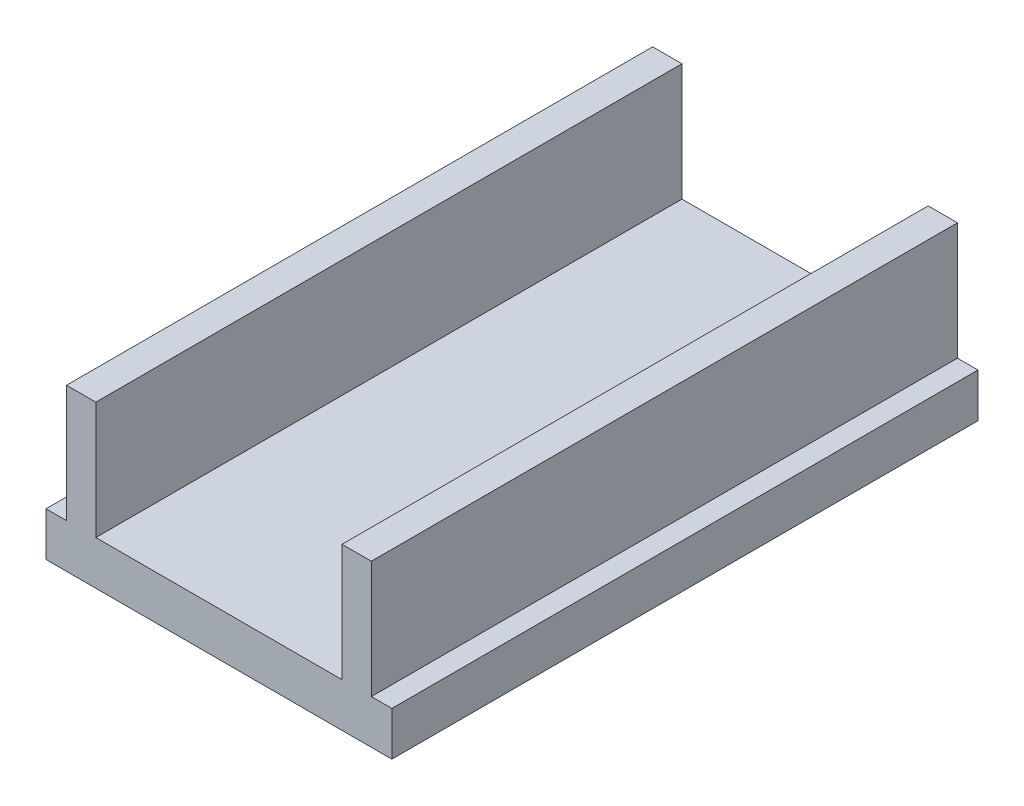
SolidWorks part; units mm, degrees
ref_plane "Front Plane" through (0, 0, 0) normal (0, 0, 1) x (1, 0, 0)
ref_plane "Top Plane" through (0, 0, 0) normal (0, 1, 0) x (1, 0, 0)
ref_plane "Right Plane" through (0, 0, 0) normal (1, 0, 0) x (0, 0, -1)
sketch "Sketch1" plane through (0, 0, 0) normal (0, 1, 0) x (1, 0, 0)
  line L0 (-5.5819, 12.8456) -> (-5.5819, -7.1544)
  line L1 (-6.2819, 12.8456) -> (5.5181, 12.8456)
  line L2 (-6.2819, 12.8456) -> (-6.2819, -7.1544)
  line L3 (-6.2819, -7.1544) -> (5.5181, -7.1544)
  line L4 (5.5181, 12.8456) -> (5.5181, -7.1544)
  line L5 (-5.5819, -7.1544) -> (4.8181, -7.1544)
  line L6 (4.8181, -7.1544) -> (4.8181, 12.8456)
  line L7 (4.8181, 12.8456) -> (-4.5819, 12.8456)
  line L8 (-4.5819, 12.8456) -> (-4.5819, -7.1544)
  line L9 (3.8181, 12.8456) -> (3.8181, -7.1544)
  dimension "D1" = 11.8
  dimension "D2" = 0.7
  dimension "D3" = 1
  dimension "D4" = 1
  dimension "D5" = 0.7
  dimension "D6" = 20
extrude "Boss-Extrude1" add sketch "Sketch1" along normal blind 1.5 contours L2 L3 L0 L1 | L8 L1 L0 L3 | L9 L1 L8 L5 | L7 L9 L3 L6 | L6 L3 L4 L1 region at (-5.0819, 0, -2.8456) region at (-5.9319, 0, -2.8456) region at (-0.3819, 0, -2.8456) region at (4.3181, 0, -2.8456) region at (5.1681, 0, -2.8456)
extrude "Boss-Extrude2" add sketch "Sketch1<3>" along normal blind 4 from surface contours L8 L1 L0 L3 | L7 L9 L3 L6 region at (-5.0819, 0, -2.8456) region at (4.3181, 0, -2.8456) starting at face at (-0.3819, 1.5, -2.8456)
sketch "Sketch1<3>" plane through (0, 0, 0) normal (0, 1, 0) x (1, 0, 0) same geometry as "Sketch1"
